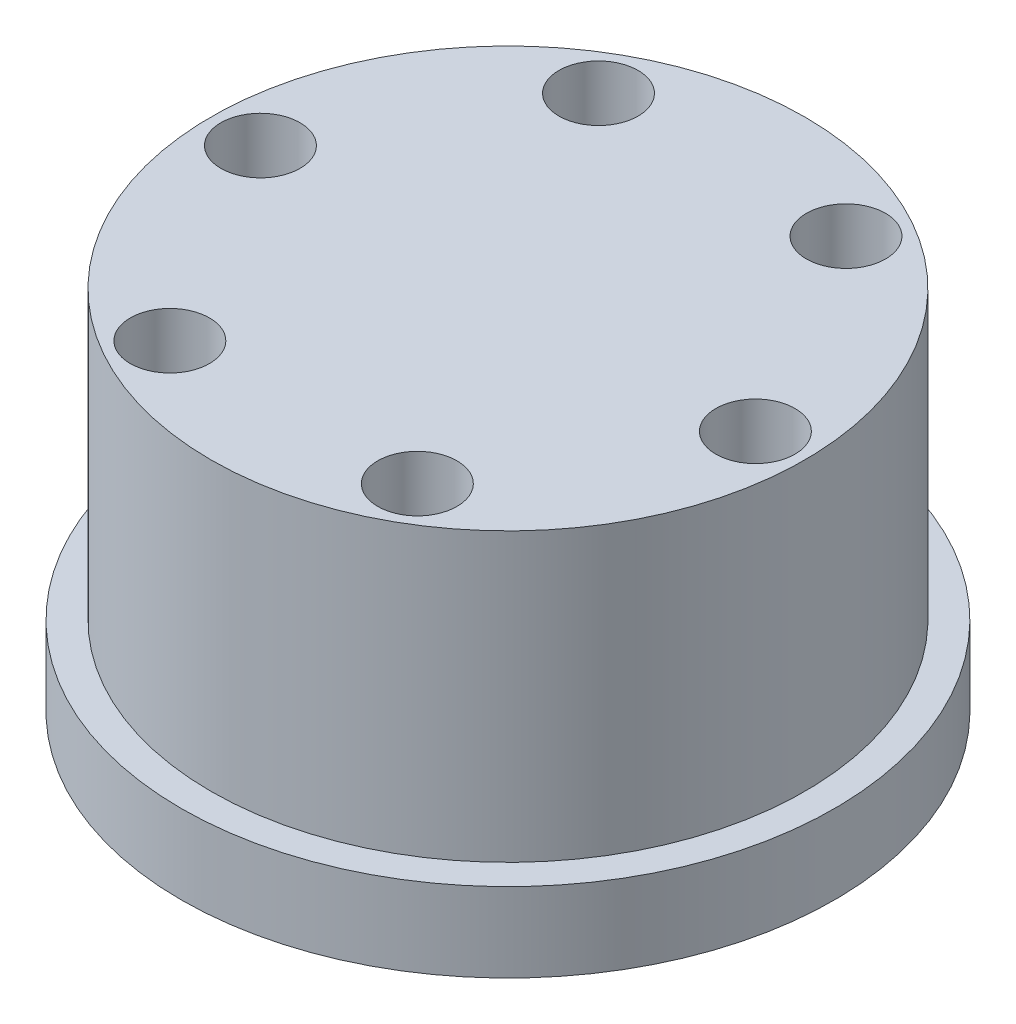
SolidWorks part; units mm, degrees
ref_plane "Front Plane" through (0, 0, 0) normal (0, 0, 1) x (1, 0, 0)
ref_plane "Top Plane" through (0, 0, 0) normal (0, 1, 0) x (1, 0, 0)
ref_plane "Right Plane" through (0, 0, 0) normal (1, 0, 0) x (0, 0, -1)
sketch "Sketch1" plane through (0, 0, 0) normal (0, 1, 0) x (1, 0, 0)
  circle A0 centre (0, 0) radius 16.5
  circle A1 centre (0, 0) radius 12.5 construction
  circle A2 centre (0, 12.5) radius 1.5
  circle A3 centre (10.8253, 6.25) radius 1.5
  circle A4 centre (10.8253, -6.25) radius 1.5
  circle A5 centre (0, -12.5) radius 1.5
  circle A6 centre (-10.8253, -6.25) radius 1.5
  circle A7 centre (-10.8253, 6.25) radius 1.5
  point P19 (0, 0)
  dimension "D1" = 33
  dimension "D2" = 25
  dimension "D3" = 3
  dimension "D4" = 6
extrude "Boss-Extrude1" add sketch "Sketch1" along normal blind 4
sketch "Sketch2" plane through (0, 4, 0) normal (0, 1, 0) x (1, 0, 0)
  circle A0 centre (0, 0) radius 15
  dimension "D1" = 30
extrude "Boss-Extrude2" add sketch "Sketch2" along normal blind 14.5
sketch "Sketch5" plane through (0, 18.5, 0) normal (0, 1, 0) x (1, 0, 0)
  circle A0 centre (0, 0) radius 12.5 construction
  circle A1 centre (-12.5, 0) radius 2
  circle A2 centre (-6.25, 10.8253) radius 2
  circle A3 centre (6.25, 10.8253) radius 2
  circle A4 centre (12.5, 0) radius 2
  circle A5 centre (6.25, -10.8253) radius 2
  circle A6 centre (-6.25, -10.8253) radius 2
  point P17 (0, 0)
  dimension "D1" = 25
  dimension "D2" = 4
  dimension "D3" = 6
extrude "Cut-Extrude3" cut sketch "Sketch5" against normal blind 6.5
sketch "Sketch6" plane through (0, 0, 0) normal (0, -1, 0) x (1, 0, 0)
  circle A0 centre (0, 0) radius 7.5
  dimension "D1" = 15
extrude "Cut-Extrude4" cut sketch "Sketch6" against normal blind 5
